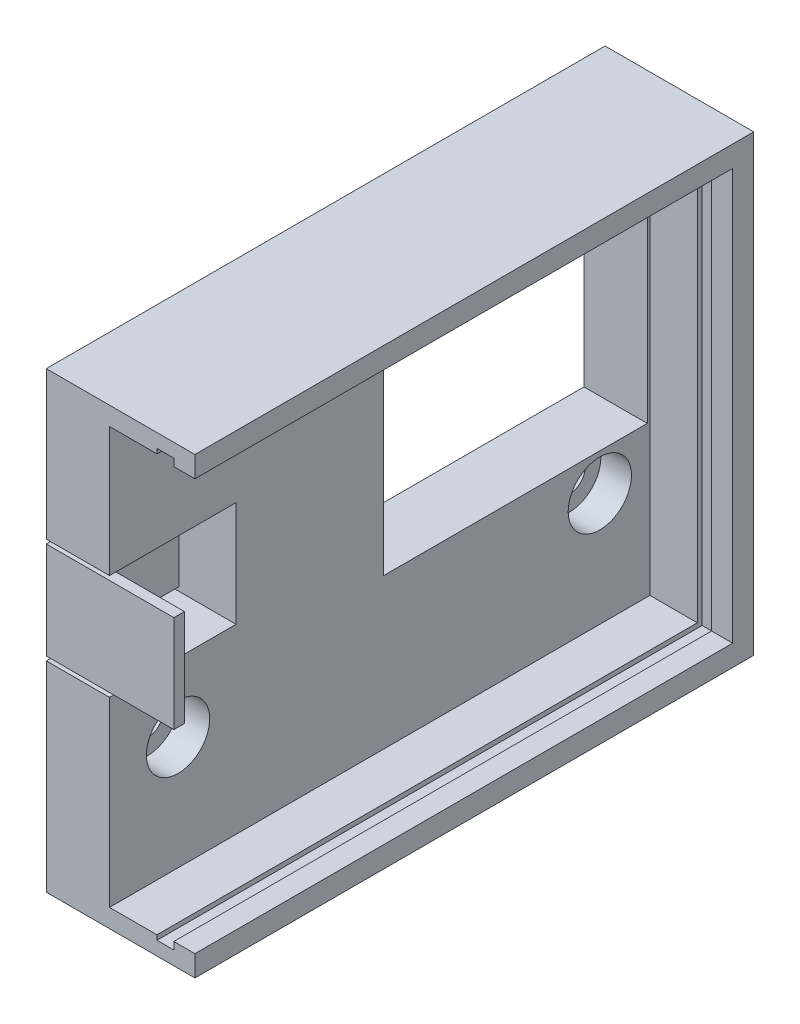
SolidWorks part; units mm, degrees
ref_plane "Front Plane" through (0, 0, 0) normal (1, 0, 0) x (0, 1, 0)
ref_plane "Top Plane" through (0, 0, 0) normal (0, 0, 1) x (0, 1, 0)
ref_plane "Right Plane" through (0, 0, 0) normal (0, 1, 0) x (-1, 0, 0)
sketch "Sketch1" plane through (0, 0, 0) normal (1, 0, 0) x (0, 1, 0)
  line L14 (-11.7365, -20.1625) -> (-11.7365, 19.8375) construction
  line L15 (-24.2365, 26.3375) -> (-24.2365, -26.6625)
  line L16 (-24.2365, 26.3375) -> (18.7635, 26.3375)
  line L17 (-24.2365, -26.6625) -> (18.7635, -26.6625)
  line L18 (18.7635, -26.6625) -> (18.7635, 26.3375)
  circle A0 centre (-11.7365, -20.1625) radius 1.524
  circle A1 centre (-11.7365, 19.8375) radius 1.524
  point P0 (11.2635, -20.5112)
  dimension "D1" = 40
  dimension "D2" = 43
  dimension "D3" = 12.5
  dimension "D4" = 6.5
  dimension "D5" = 53
extrude "Boss-Extrude1" add sketch "Sketch1" along normal blind 6
sketch "Sketch3" plane through (6, 0, 0) normal (1, 0, 0) x (0, 1, 0)
  line L0 (-24.2365, 26.3375) -> (18.7635, -26.6625) construction
  line L5 (18.7635, -26.6625) -> (18.7635, 26.3375) construction
  line L6 (18.7635, 26.3375) -> (-24.2365, -26.6625) construction
  line L7 (-22.4865, 24.5875) -> (-22.4865, 26.3375)
  line L15 (-22.4865, 24.5875) -> (-22.4865, -24.9125)
  line L16 (-22.4865, -24.9125) -> (17.0135, -24.9125)
  line L19 (17.0135, 24.5875) -> (17.0135, -24.9125)
  line L20 (-22.4865, 24.5875) -> (17.0135, -24.9125) construction
  line L21 (-22.4865, -24.9125) -> (17.0135, 24.5875) construction
  line L22 (-24.2365, 26.3375) -> (-22.4865, 26.3375)
  line L23 (-24.2365, 26.3375) -> (-24.2365, -26.6625)
  line L24 (-24.2365, -26.6625) -> (18.7635, -26.6625)
  line L25 (18.7635, 26.3375) -> (18.7635, -26.6625)
  line L26 (-24.2365, 26.3375) -> (18.7635, -26.6625) construction
  line L27 (-24.2365, -26.6625) -> (18.7635, 26.3375) construction
  line L28 (17.0135, 24.5875) -> (17.0135, 26.3375)
  line L29 (17.0135, 26.3375) -> (18.7635, 26.3375)
  point P2 (-2.7365, -0.1625)
  point P9 (-2.7365, -0.1625)
  dimension "D1" = 49.5
  dimension "D2" = 39.5
extrude "Boss-Extrude2" add sketch "Sketch3" along normal blind 4.5
sketch "Sketch5" plane through (10.5, 0, 0) normal (1, 0, 0) x (0, 1, 0)
  line L0 (-24.2365, 26.3375) -> (18.7635, -26.6625) construction
  line L1 (18.7635, -26.6625) -> (18.7635, 26.3375) construction
  line L7 (18.7635, 26.3375) -> (-24.2365, -26.6625) construction
  line L8 (-22.9365, 25.0375) -> (-22.9365, 26.3375)
  line L14 (-22.9365, 25.0375) -> (-22.9365, -25.3625)
  line L18 (-22.9365, -25.3625) -> (17.4635, -25.3625)
  line L19 (17.4635, 25.0375) -> (17.4635, -25.3625)
  line L20 (-22.9365, 25.0375) -> (17.4635, -25.3625) construction
  line L21 (-22.9365, -25.3625) -> (17.4635, 25.0375) construction
  line L22 (-24.2365, 26.3375) -> (-22.9365, 26.3375)
  line L23 (-24.2365, 26.3375) -> (-24.2365, -26.6625)
  line L24 (-24.2365, -26.6625) -> (18.7635, -26.6625)
  line L25 (18.7635, 26.3375) -> (18.7635, -26.6625)
  line L26 (-24.2365, 26.3375) -> (18.7635, -26.6625) construction
  line L27 (-24.2365, -26.6625) -> (18.7635, 26.3375) construction
  line L28 (17.4635, 25.0375) -> (17.4635, 26.3375)
  line L29 (17.4635, 26.3375) -> (18.7635, 26.3375)
  point P4 (-2.7365, -0.1625)
  point P13 (-2.7365, -0.1625)
  dimension "D1" = 50.4
  dimension "D2" = 40.4
extrude "Boss-Extrude3" add sketch "Sketch5" along normal blind 1.6 contours L14 L18 L19 L28 L29 L25 L24 L23 L22 L8
sketch "Sketch6" plane through (12.1, 0, 0) normal (1, 0, 0) x (0, 1, 0)
  line L4 (-24.2365, 26.3375) -> (18.7635, -26.6625) construction
  line L5 (18.7635, -26.6625) -> (18.7635, 26.3375) construction
  line L11 (18.7635, 26.3375) -> (-24.2365, -26.6625) construction
  line L12 (-22.2365, 24.3375) -> (-22.2365, 26.3375)
  line L16 (-22.2365, 24.3375) -> (-22.2365, -24.6625)
  line L17 (-22.2365, -24.6625) -> (16.7635, -24.6625)
  line L18 (16.7635, 24.3375) -> (16.7635, -24.6625)
  line L19 (-22.2365, 24.3375) -> (16.7635, -24.6625) construction
  line L20 (-22.2365, -24.6625) -> (16.7635, 24.3375) construction
  line L21 (-24.2365, 26.3375) -> (-22.2365, 26.3375)
  line L22 (-24.2365, 26.3375) -> (-24.2365, -26.6625)
  line L23 (-24.2365, -26.6625) -> (18.7635, -26.6625)
  line L24 (18.7635, 26.3375) -> (18.7635, -26.6625)
  line L25 (-24.2365, 26.3375) -> (18.7635, -26.6625) construction
  line L26 (-24.2365, -26.6625) -> (18.7635, 26.3375) construction
  line L27 (16.7635, 24.3375) -> (16.7635, 26.3375)
  line L28 (16.7635, 26.3375) -> (18.7635, 26.3375)
  point P2 (-2.7365, -0.1625)
  point P11 (-2.7365, -0.1625)
  dimension "D1" = 39
  dimension "D2" = 49
extrude "Boss-Extrude4" add sketch "Sketch6" along normal blind 2
sketch "Sketch7" plane through (14.1, 0, 0) normal (1, 0, 0) x (0, 1, 0)
  circle A0 centre (-11.7365, -20.1625) radius 3
  circle A1 centre (-11.7365, 19.8375) radius 3
extrude "Cut-Extrude2" cut sketch "Sketch7" against normal blind 11
sketch "Sketch8" plane through (6, 0, 0) normal (1, 0, 0) x (0, 1, 0)
  line L0 (17.0135, 26.3375) -> (-22.4865, 26.3375) construction
  line L1 (-5.2365, 26.3375) -> (4.7635, 26.3375)
  line L2 (-5.2365, 26.3375) -> (-5.2365, 14.3375)
  line L3 (-5.2365, 14.3375) -> (4.7635, 14.3375)
  line L4 (4.7635, 26.3375) -> (4.7635, 14.3375)
  line L7 (-24.2365, 26.3375) -> (-24.2365, -26.6625) construction
  dimension "D1" = 19
  dimension "D2" = 10
  dimension "D3" = 12
extrude "Cut-Extrude3" cut sketch "Sketch8" against normal blind 5.4
sketch "Sketch9" plane through (0.6, 0, 0) normal (1, 0, 0) x (0, 1, 0)
  line L0 (-5.2365, 14.3375) -> (4.7635, 14.3375) construction
  line L1 (-5.2365, 26.3375) -> (-4.8365, 26.3375)
  line L2 (-5.2365, 26.3375) -> (-5.2365, 14.3375)
  line L3 (-5.2365, 14.3375) -> (-4.8365, 14.3375)
  line L4 (-4.8365, 26.3375) -> (-4.8365, 14.3375)
  line L5 (-0.2365, 14.3375) -> (-0.2365, 27.5426) construction
  line L6 (-5.2365, 14.3375) -> (4.7635, 14.3375) construction
  line L7 (4.3635, 26.3375) -> (4.3635, 14.3375)
  line L8 (4.7635, 14.3375) -> (4.3635, 14.3375)
  line L9 (4.7635, 26.3375) -> (4.7635, 14.3375)
  line L10 (4.7635, 26.3375) -> (4.3635, 26.3375)
  dimension "D1" = 0.4
extrude "Cut-Extrude4" cut sketch "Sketch9" against normal blind 5.5
sketch "Sketch10" plane through (0.6, 0, 0) normal (1, 0, 0) x (0, 1, 0)
  line L0 (4.3635, 26.3375) -> (4.3635, 14.3375) construction
  line L1 (-4.8365, 26.3375) -> (4.3635, 26.3375)
  line L2 (-4.8365, 26.3375) -> (-4.8365, 25.3375)
  line L3 (-4.8365, 25.3375) -> (4.3635, 25.3375)
  line L4 (4.3635, 26.3375) -> (4.3635, 25.3375)
  dimension "D1" = 1
extrude "Boss-Extrude5" add sketch "Sketch10" along normal blind 11.5
sketch "Sketch11" plane through (6, 0, 0) normal (1, 0, 0) x (0, 1, 0)
  line L1 (16.7635, -24.6625) -> (-8.2365, -24.6625)
  line L2 (16.7635, -24.6625) -> (16.7635, 0.3375)
  line L3 (16.7635, 0.3375) -> (-8.2365, 0.3375)
  line L4 (-8.2365, -24.6625) -> (-8.2365, 0.3375)
  point P5 (19.5021, -24.6625)
  point P6 (16.7635, -24.6625)
  dimension "D1" = 25
  dimension "D2" = 25
extrude "Cut-Extrude5" cut sketch "Sketch11" against normal blind 11.5
sketch "Sketch13" plane through (14.1, 0, 0) normal (1, 0, 0) x (0, 1, 0)
